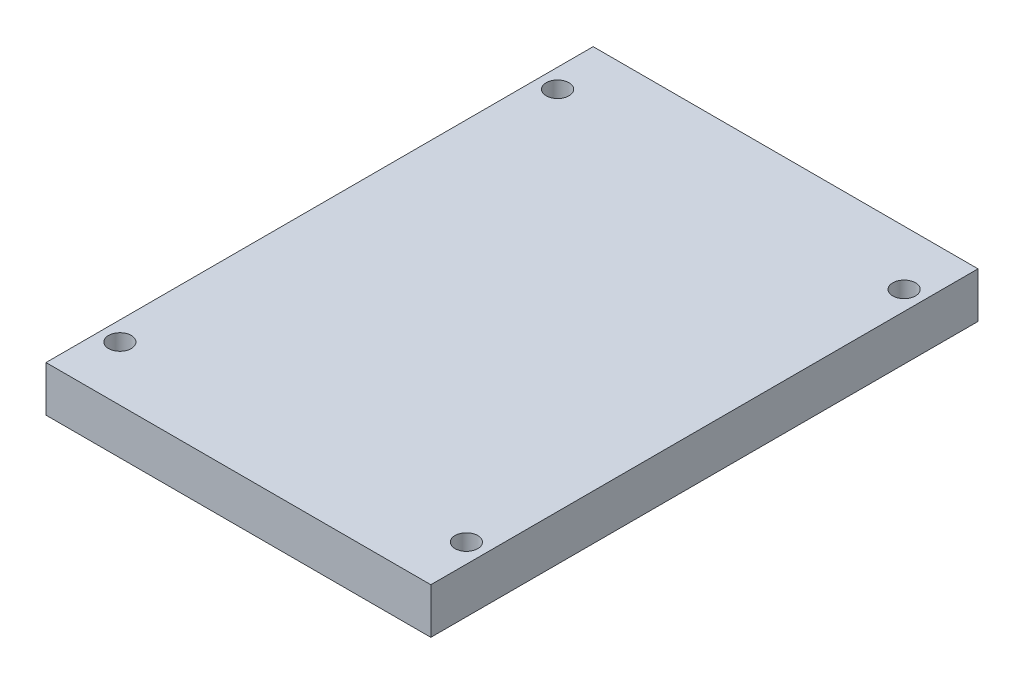
SolidWorks part; units mm, degrees
ref_plane "Front Plane" through (0, 0, 0) normal (0, 0, 1) x (1, 0, 0)
ref_plane "Top Plane" through (0, 0, 0) normal (0, 1, 0) x (1, 0, 0)
ref_plane "Right Plane" through (0, 0, 0) normal (1, 0, 0) x (0, 0, -1)
sketch "Sketch1" plane through (0, 0, 0) normal (0, 1, 0) x (1, 0, 0)
  line L1 (0, 0) -> (-54.61, 0)
  line L2 (0, 0) -> (0, 76.2)
  line L3 (0, 76.2) -> (-54.61, 76.2)
  line L4 (-54.61, 0) -> (-54.61, 76.2)
  dimension "D1" = 76.2
  dimension "D2" = 54.61
extrude "Boss-Extrude1" add sketch "Sketch1" along normal blind 6.35
sketch "Sketch2" plane through (0, 6.35, 0) normal (0, 1, 0) x (1, 0, 0)
  line L0 (0, 0) -> (0, 76.2) construction
  line L1 (-54.61, 0) -> (0, 0) construction
  circle A0 centre (-3.175, 7.62) radius 1.5875
  circle A4 centre (-3.175, 68.58) radius 1.5875
  dimension "D2" = 3.175
  dimension "D1" = 3.175
  dimension "D3" = 7.62
  dimension "D4" = 68.58
extrude "Cut-Extrude1" cut sketch "Sketch2" against normal through all
ref_plane "KORAL!!!" through (-27.305, 0, 0) normal (1, 0, 0) x (0, 0, -1)
mirror "Mirror1" about plane through (-27.305, 0, 0) normal (1, 0, 0) of "Cut-Extrude1"
sketch "Sketch3" plane through (0, 6.35, 0) normal (0, 1, 0) x (1, 0, 0)
  line L0 (0, 0) -> (-0.508, 0)
  line L1 (-54.61, 0) -> (0, 0) construction
  line L2 (-0.508, 0) -> (-0.508, 76.2)
  line L3 (0, 76.2) -> (-54.61, 76.2) construction
  line L4 (-0.508, 76.2) -> (0, 76.2)
  line L5 (0, 76.2) -> (0, 0)
  dimension "D1" = 0.508
extrude "Cut-Extrude2" cut sketch "Sketch3" against normal through all
mirror "Mirror2" about plane through (-27.305, 0, 0) normal (1, 0, 0) of "Cut-Extrude2"
